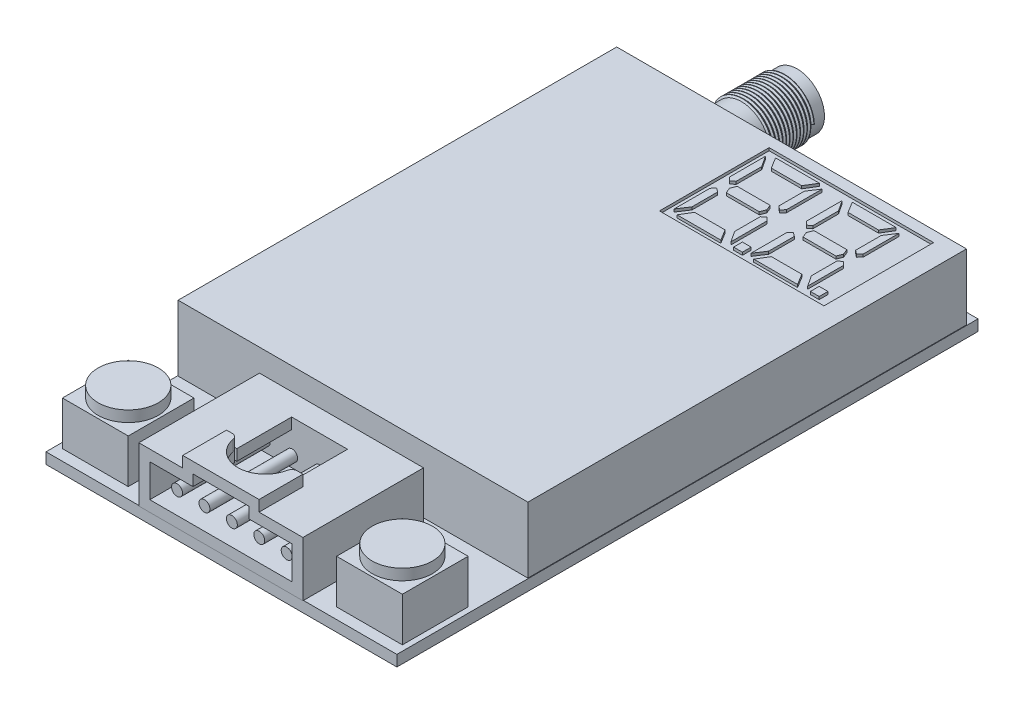
SolidWorks part; units mm, degrees
ref_plane "Ön Düzlem" through (0, 0, 0) normal (0, 0, 1) x (1, 0, 0)
ref_plane "Üst Düzlem" through (0, 0, 0) normal (0, 1, 0) x (1, 0, 0)
ref_plane "Sağ Düzlem" through (0, 0, 0) normal (1, 0, 0) x (0, 0, -1)
sketch "Çizim1" plane through (0, 0, 0) normal (0, 1, 0) x (1, 0, 0)
  line L1 (16, -26.5) -> (-16, -26.5)
  line L2 (16, -26.5) -> (16, 26.5)
  line L3 (16, 26.5) -> (-16, 26.5)
  line L4 (-16, -26.5) -> (-16, 26.5)
  line L5 (16, -26.5) -> (-16, 26.5) construction
  line L6 (16, 26.5) -> (-16, -26.5) construction
  point P0 (0, 0)
  dimension "D1" = 32
  dimension "D2" = 53
extrude "Yükseklik-Ekstrüzyon1" add sketch "Çizim1" along normal blind 1
sketch "Çizim2" plane through (0, 1, 0) normal (0, 1, 0) x (1, 0, 0)
  line L1 (-15.95, 25.5) -> (15.95, 25.5)
  line L2 (-15.95, 25.5) -> (-15.95, -14.5)
  line L3 (-15.95, -14.5) -> (15.95, -14.5)
  line L4 (15.95, 25.5) -> (15.95, -14.5)
  line L6 (16, 26.5) -> (-16, 26.5) construction
  line L7 (-16, 26.5) -> (-16, -26.5) construction
  line L8 (16, -26.5) -> (16, 26.5) construction
  dimension "D1" = 1
  dimension "D2" = 0.05
  dimension "D3" = 0.05
  dimension "D4" = 40
extrude "Yükseklik-Ekstrüzyon2" add sketch "Çizim2" along normal blind 6 separate body
sketch "Çizim3" plane through (0, 1, 0) normal (0, 1, 0) x (1, 0, 0)
  line L0 (16, -26.5) -> (16, 26.5) construction
  line L1 (15.5, -25.5) -> (9.5, -25.5)
  line L2 (15.5, -25.5) -> (15.5, -19.5)
  line L3 (15.5, -19.5) -> (9.5, -19.5)
  line L4 (9.5, -25.5) -> (9.5, -19.5)
  line L5 (15.5, -25.5) -> (9.5, -19.5) construction
  line L6 (15.5, -19.5) -> (9.5, -25.5) construction
  line L7 (-16, -26.5) -> (16, -26.5) construction
  line L8 (0, 0) -> (0, -34.6384) construction
  line L9 (-15.5, -25.5) -> (-9.5, -25.5)
  line L10 (-15.5, -25.5) -> (-15.5, -19.5)
  line L11 (-15.5, -19.5) -> (-9.5, -25.5) construction
  line L12 (-15.5, -25.5) -> (-9.5, -19.5) construction
  line L13 (-15.5, -19.5) -> (-9.5, -19.5)
  line L14 (-9.5, -25.5) -> (-9.5, -19.5)
  point P0 (12.5, -22.5)
  dimension "D1" = 0.5
  dimension "D2" = 1
  dimension "D3" = 6
extrude "Yükseklik-Ekstrüzyon5" add sketch "Çizim3" along normal blind 4
sketch "Çizim7" plane through (0, 5, 0) normal (0, 1, 0) x (1, 0, 0)
  line L0 (-12.5, -19.5) -> (-12.5, -25.5) construction
  line L1 (-9.5, -19.5) -> (-15.5, -19.5) construction
  line L2 (-15.5, -25.5) -> (-9.5, -25.5) construction
  line L3 (0, 0) -> (0, -43.4211) construction
  circle A0 centre (-12.5, -22.5) radius 2.75
  circle A1 centre (12.5, -22.5) radius 2.75
  dimension "D1" = 5.5
extrude "Yükseklik-Ekstrüzyon6" add sketch "Çizim7" along normal blind 1
sketch "Çizim11" plane through (0, 0, 26.5) normal (0, 0, 1) x (1, 0, 0)
  line L0 (-7.481, 1) -> (7.481, 1)
  line L1 (7.481, 1) -> (7.481, 6)
  line L2 (-7.481, 6) -> (7.481, 6)
  line L6 (-7.481, 1) -> (-7.481, 6)
  point P3 (0, 1)
  point P11 (0, 7)
  dimension "D1" = 5
extrude "Yükseklik-Ekstrüzyon8" add sketch "Çizim11" against normal blind 11 from offset 0.05 separate body
sketch "Çizim15" plane through (0, 0, 26.55) normal (0, 0, 1) x (1, 0, 0)
  line L0 (0, 6) -> (3.481, 6)
  line L1 (7.481, 6) -> (-7.481, 6) construction
  line L2 (3.481, 6) -> (3.481, 7)
  line L3 (3.481, 7) -> (-3.481, 7)
  line L4 (-3.481, 7) -> (-3.481, 6)
  line L5 (-3.481, 6) -> (0, 6)
  dimension "D1" = 4
  dimension "D2" = 1
extrude "Yükseklik-Ekstrüzyon9" add sketch "Çizim15" against normal blind 4
sketch "Çizim16" plane through (0, 7, 0) normal (0, 1, 0) x (1, 0, 0)
  line L0 (2.958, -22.55) -> (2, -22.55)
  line L1 (-2, -22.55) -> (-2, -17.55)
  line L2 (-2, -17.55) -> (2, -17.55)
  line L3 (-2, -22.55) -> (-2.958, -22.55)
  line L4 (3.481, -26.55) -> (-3.481, -26.55) construction
  line L5 (2, -17.55) -> (2, -22.55)
  line L6 (3.481, -22.55) -> (-3.481, -22.55) construction
  arc A0 (-2.4668, -22.9569) -> (-2.958, -22.55) centre (-2.958, -23.05) ccw
  arc A1 (-2.4668, -22.9569) -> (2.4668, -22.9569) centre (0, -22.4893) ccw
  arc A2 (2.4668, -22.9569) -> (2.958, -22.55) centre (2.958, -23.05) cw
  point P2 (0, -26.55)
  point P3 (0, -20.2825)
  point P10 (0, -25)
  dimension "D1" = 0.5
  dimension "D4" = 5
  dimension "D5" = 4
extrude "Kes-Ekstrüzyon2" cut sketch "Çizim16" against normal blind 4
sketch "Çizim12" plane through (0, 0, 26.55) normal (0, 0, 1) x (1, 0, 0)
  line L0 (-6.481, 2) -> (6.481, 2)
  line L1 (6.481, 2) -> (6.481, 5)
  line L2 (6.481, 5) -> (2.5478, 5)
  line L3 (2.5478, 5) -> (2.5478, 6.0048)
  line L4 (2.5478, 6.0048) -> (-2.5478, 6.0048)
  line L10 (0, 1) -> (0, 16.1084) construction
  line L11 (-6.481, 2) -> (-6.481, 5)
  line L12 (-2.5478, 5) -> (-2.5478, 6.0048)
  line L13 (-6.481, 5) -> (-2.5478, 5)
  point P21 (0, 2)
  point P22 (0, 6.0048)
extrude "Kes-Ekstrüzyon1" cut sketch "Çizim12" against normal blind 9
sketch "Çizim18" plane through (0, 0, -26.5) normal (0, 0, -1) x (-1, 0, 0)
  line L0 (16, 1) -> (16, 0) construction
  line L1 (13, -2.5) -> (7, -2.5)
  line L2 (13, -2.5) -> (13, 3.5)
  line L3 (13, 3.5) -> (7, 3.5)
  line L4 (7, -2.5) -> (7, 3.5)
  line L5 (13, -2.5) -> (7, 3.5) construction
  line L6 (13, 3.5) -> (7, -2.5) construction
  point P0 (10, 0.5)
  point P7 (16, 0.5)
  point P8 (13, 0.5)
  dimension "D1" = 6
  dimension "D2" = 3
extrude "Yükseklik-Ekstrüzyon11" add sketch "Çizim18" along normal blind 1.5
sketch "Çizim19" plane through (0, 0, -28) normal (0, 0, -1) x (-1, 0, 0)
  line L0 (7, 0.5) -> (13, 0.5) construction
  line L1 (7, 3.5) -> (7, -2.5) construction
  line L2 (13, -2.5) -> (13, 3.5) construction
  circle A0 centre (10, 0.5) radius 2.5
  dimension "D1" = 5
extrude "Yükseklik-Ekstrüzyon12" add sketch "Çizim19" along normal blind 8
sketch "Çizim20" plane through (0, 0, -36) normal (0, 0, -1) x (-1, 0, 0)
  circle A0 centre (10, 0.5) radius 2.25
  circle A1 centre (10, 0.5) radius 0.5
  dimension "D1" = 4.5
  dimension "D2" = 1
extrude "Kes-Ekstrüzyon3" cut sketch "Çizim20" against normal blind 3
thread "MinColWidth_OnTracking1" pitch 0.3175 method extrude profile "HeaderRowsCount1" start angle 0, offset 1, length 4, pitch 0.3175, diameter 5
ref_plane "Düzlem1" through (-7.5, 0.5, -35) normal (0, -1, 0) x (1, 0, 0)
sketch "HeaderRowsCount1" plane through (-7.5, 0.5, -35) normal (0, -1, 0) x (1, 0, 0)
  line L0 (0, 0) -> (0, 0.3175) construction
  line L1 (0, 0) -> (0.1719, 0.0992)
  line L2 (0.1719, 0.0992) -> (0.1719, 0.1389)
  line L3 (0.1719, 0.1389) -> (0, 0.2381)
  line L4 (0.1719, 0.1191) -> (0, 0.1191) construction
  line L11 (0, 0) -> (0, 0.2381)
  point P2 (0, 0)
  dimension "Pitch" = 0.3175
  dimension "Profile_Angle" = 60
  dimension "Profile_Land" = 0.0397
  dimension "Profile_Height" = 0.1719
sketch "Çizim25" plane through (0, 7, 0) normal (0, 1, 0) x (1, 0, 0)
  line L0 (15.95, 25.5) -> (-15.95, 25.5) construction
  line L1 (13.95, 24.5) -> (-1.05, 24.5)
  line L2 (13.95, 24.5) -> (13.95, 14.5)
  line L3 (13.95, 14.5) -> (-1.05, 14.5)
  line L4 (-1.05, 24.5) -> (-1.05, 14.5)
  line L5 (15.95, -14.5) -> (15.95, 25.5) construction
  dimension "D1" = 1
  dimension "D2" = 2
  dimension "D3" = 15
  dimension "D4" = 10
extrude "Kes-Ekstrüzyon4" cut sketch "Çizim25" against normal blind 0.25
sketch "Çizim27" plane through (0, 6.75, 0) normal (0, 1, 0) x (1, 0, 0)
  line L0 (0.0534, 14.9926) -> (4.0534, 14.9926)
  line L2 (3.442, 15.9926) -> (0.6648, 15.9926)
  line L3 (0.6648, 15.9926) -> (0.0534, 14.9926)
  line L4 (0.107, 16.3055) -> (-0.5365, 15.3258)
  line L5 (-0.5365, 15.3258) -> (-0.5365, 18.5945)
  line L6 (0.107, 16.3055) -> (0.107, 18.6397)
  line L7 (-0.5365, 18.5945) -> (-0.2353, 18.9027)
  line L8 (-0.2353, 18.9027) -> (0.107, 18.6397)
  line L9 (0.6648, 18.9878) -> (3.442, 18.9878)
  line L10 (0.5534, 19.9878) -> (3.5534, 19.9878)
  line L11 (5.1894, 15.8242) -> (5.9894, 15.8242)
  line L12 (5.1894, 15.8242) -> (5.1894, 15.0242)
  line L13 (5.1894, 15.0242) -> (5.9894, 15.0242)
  line L14 (0.3553, 19.4878) -> (0.5534, 19.9878)
  line L15 (5.9894, 15.8242) -> (5.9894, 15.0242)
  line L16 (3.7515, 19.4878) -> (3.5534, 19.9878)
  line L18 (4.3421, 18.9027) -> (3.9997, 18.6397)
  line L19 (4.6432, 18.5945) -> (4.3421, 18.9027)
  line L20 (3.9997, 16.3055) -> (3.9997, 18.6397)
  line L21 (4.6432, 15.3258) -> (4.6432, 18.5945)
  line L22 (3.9997, 16.3055) -> (4.6432, 15.3258)
  line L23 (3.442, 15.9926) -> (4.0534, 14.9926)
  line L24 (0.6648, 15.9926) -> (3.442, 15.9926)
  line L26 (4.0534, 14.9926) -> (0.0534, 14.9926)
  line L27 (4.0534, 23.983) -> (0.0534, 23.983)
  line L28 (7.0534, 14.9926) -> (11.0534, 14.9926)
  line L29 (0.6648, 22.983) -> (3.442, 22.983)
  line L30 (3.442, 22.983) -> (4.0534, 23.983)
  line L31 (3.9997, 22.6702) -> (4.6432, 23.6498)
  line L32 (4.6432, 23.6498) -> (4.6432, 20.3812)
  line L33 (3.9997, 22.6702) -> (3.9997, 20.336)
  line L34 (4.6432, 20.3812) -> (4.3421, 20.073)
  line L35 (4.3421, 20.073) -> (3.9997, 20.336)
  line L36 (10.442, 15.9926) -> (7.6648, 15.9926)
  line L37 (3.7515, 19.4878) -> (3.5534, 18.9878)
  line L38 (0.3553, 19.4878) -> (0.5534, 18.9878)
  line L39 (7.6648, 15.9926) -> (7.0534, 14.9926)
  line L40 (0.5534, 18.9878) -> (3.5534, 18.9878)
  line L41 (0.6648, 19.9878) -> (3.442, 19.9878)
  line L42 (-0.2353, 20.073) -> (0.107, 20.336)
  line L43 (-0.5365, 20.3812) -> (-0.2353, 20.073)
  line L44 (0.107, 22.6702) -> (0.107, 20.336)
  line L45 (-0.5365, 23.6498) -> (-0.5365, 20.3812)
  line L46 (0.107, 22.6702) -> (-0.5365, 23.6498)
  line L47 (0.6648, 22.983) -> (0.0534, 23.983)
  line L48 (3.442, 22.983) -> (0.6648, 22.983)
  line L49 (7.107, 16.3055) -> (6.4635, 15.3258)
  line L50 (0.0534, 23.983) -> (4.0534, 23.983)
  line L51 (6.4635, 15.3258) -> (6.4635, 18.5945)
  line L52 (7.107, 16.3055) -> (7.107, 18.6397)
  line L53 (6.4635, 18.5945) -> (6.7647, 18.9027)
  line L54 (6.7647, 18.9027) -> (7.107, 18.6397)
  line L55 (7.6648, 18.9878) -> (10.442, 18.9878)
  line L56 (7.5534, 19.9878) -> (10.5534, 19.9878)
  line L57 (12.1894, 15.8242) -> (12.9894, 15.8242)
  line L58 (12.1894, 15.8242) -> (12.1894, 15.0242)
  line L59 (12.1894, 15.0242) -> (12.9894, 15.0242)
  line L60 (7.3553, 19.4878) -> (7.5534, 19.9878)
  line L61 (12.9894, 15.8242) -> (12.9894, 15.0242)
  line L62 (10.7515, 19.4878) -> (10.5534, 19.9878)
  line L63 (11.3421, 18.9027) -> (10.9997, 18.6397)
  line L64 (11.6432, 18.5945) -> (11.3421, 18.9027)
  line L65 (10.9997, 16.3055) -> (10.9997, 18.6397)
  line L66 (11.6432, 15.3258) -> (11.6432, 18.5945)
  line L67 (10.9997, 16.3055) -> (11.6432, 15.3258)
  line L68 (10.442, 15.9926) -> (11.0534, 14.9926)
  line L69 (7.6648, 15.9926) -> (10.442, 15.9926)
  line L70 (11.0534, 14.9926) -> (7.0534, 14.9926)
  line L71 (11.0534, 23.983) -> (7.0534, 23.983)
  line L72 (7.6648, 22.983) -> (10.442, 22.983)
  line L73 (10.442, 22.983) -> (11.0534, 23.983)
  line L74 (10.9997, 22.6702) -> (11.6432, 23.6498)
  line L75 (11.6432, 23.6498) -> (11.6432, 20.3812)
  line L76 (10.9997, 22.6702) -> (10.9997, 20.336)
  line L77 (11.6432, 20.3812) -> (11.3421, 20.073)
  line L78 (11.3421, 20.073) -> (10.9997, 20.336)
  line L79 (10.7515, 19.4878) -> (10.5534, 18.9878)
  line L80 (7.3553, 19.4878) -> (7.5534, 18.9878)
  line L81 (7.5534, 18.9878) -> (10.5534, 18.9878)
  line L82 (7.6648, 19.9878) -> (10.442, 19.9878)
  line L83 (6.7647, 20.073) -> (7.107, 20.336)
  line L84 (6.4635, 20.3812) -> (6.7647, 20.073)
  line L85 (7.107, 22.6702) -> (7.107, 20.336)
  line L86 (6.4635, 23.6498) -> (6.4635, 20.3812)
  line L87 (7.107, 22.6702) -> (6.4635, 23.6498)
  line L88 (7.6648, 22.983) -> (7.0534, 23.983)
  line L89 (10.442, 22.983) -> (7.6648, 22.983)
  line L90 (7.0534, 23.983) -> (11.0534, 23.983)
  point P2 (2.0534, 15.9926)
  point P5 (2.0534, 14.9926)
  point P15 (2.0534, 18.9878)
  point P16 (2.0534, 19.9878)
  point P64 (2.0534, 19.4878)
  point P87 (9.0534, 19.4878)
  dimension "D1" = 4
  dimension "D2" = 0.8
  dimension "D3" = 1
  dimension "D4" = 2
  dimension "D6" = 3
  dimension "D7" = 1
extrude "Yükseklik-Ekstrüzyon13" add sketch "Çizim27" along normal blind 0.25 contours L47 L29 L30 L27 | L35 L34 L32 L31 L33 | L38 L40 L9 L37 L16 L10 L14 | L44 L46 L45 L43 L42 | L8 L7 L5 L4 L6 | L23 L2 L3 L0 | L20 L22 L21 L19 L18 | L15 L11 L12 L13 | L54 L53 L51 L49 L52 | L80 L81 L55 L79 L62 L56 L60 | L85 L87 L86 L84 L83 | L88 L72 L73 L71 | L78 L77 L75 L74 L76 | L65 L67 L66 L64 L63 | L68 L36 L39 L28 | L61 L57 L58 L59 region at (2.0534, 6.75, -15.4625) region at (-0.2321, 6.75, -17.2757) region at (2.0534, 6.75, -19.4878) region at (5.5894, 6.75, -15.4242) region at (4.3388, 6.75, -17.2757) region at (2.0534, 6.75, -23.5131) region at (9.0534, 6.75, -15.4625) region at (4.3388, 6.75, -21.6999) region at (-0.2321, 6.75, -21.6999) region at (6.7679, 6.75, -17.2757) region at (9.0534, 6.75, -19.4878) region at (12.5894, 6.75, -15.4242) region at (11.3388, 6.75, -17.2757) region at (9.0534, 6.75, -23.5131) region at (11.3388, 6.75, -21.6999) region at (6.7679, 6.75, -21.6999)
sketch "Çizim28" plane through (0, 0, 17.55) normal (0, 0, 1) x (1, 0, 0)
  line L0 (-2.5478, 5) -> (2.5478, 5) construction
  line L1 (0, 5) -> (0, 1) construction
  line L2 (0, 3) -> (5, 3) construction
  line L3 (-5, 3) -> (5, 3) construction
  line L4 (5, 3) -> (2.5, 3) construction
  line L5 (2.5, 3) -> (0, 3) construction
  line L6 (0, 3) -> (-2.5, 3) construction
  line L7 (-2.5, 3) -> (-5, 3) construction
  line L8 (-7.481, 1) -> (7.481, 1) construction
  circle A0 centre (0, 3) radius 0.5
  circle A1 centre (2.5, 3) radius 0.5
  circle A2 centre (5, 3) radius 0.5
  circle A3 centre (-5, 3) radius 0.5
  circle A4 centre (-2.5, 3) radius 0.5
  point P16 (0, 3)
extrude "Yükseklik-Ekstrüzyon14" add sketch "Çizim28" along normal blind 8
